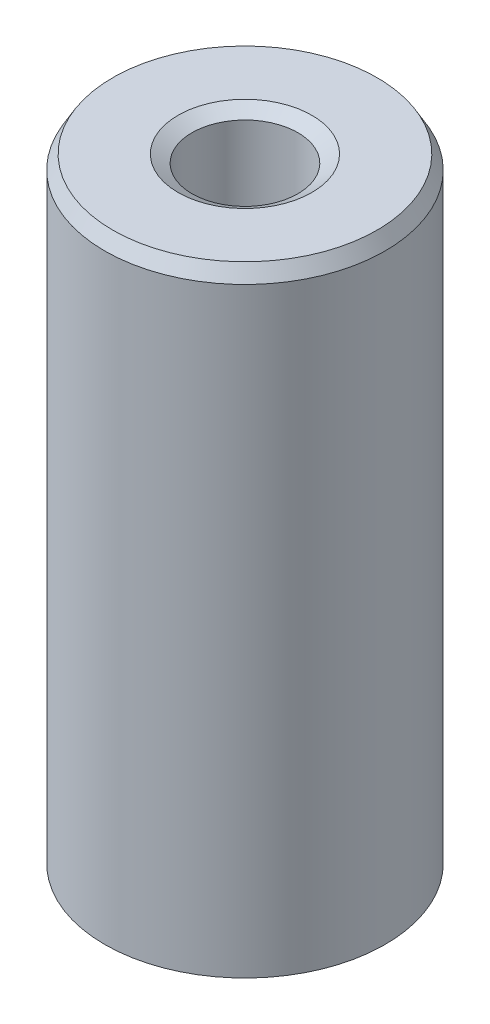
SolidWorks part; units mm, degrees
ref_plane "Front Plane" through (0, 0, 0) normal (0, 0, 1) x (1, 0, 0)
ref_plane "Top Plane" through (0, 0, 0) normal (0, 1, 0) x (1, 0, 0)
ref_plane "Right Plane" through (0, 0, 0) normal (1, 0, 0) x (0, 0, -1)
sketch "Sketch1" plane through (0, 0, 0) normal (0, 1, 0) x (1, 0, 0)
  circle A0 centre (0, 0) radius 12.5
  dimension "SLEEVE_OD" = 25
extrude "Boss-Extrude1" add sketch "Sketch1" along normal blind 55.5131
sketch "Sketch2" plane through (0, 0, 0) normal (0, 1, 0) x (1, 0, 0)
  circle A0 centre (0, 0) radius 4.7201
  dimension "BORE_D" = 9.4402
extrude "Cut-Extrude1" cut sketch "Sketch2" along normal through all
chamfer "Chamfer1" distance 1.2459 angle 30 4 edges at (0, 55.5131, 4.7201) (0, 0, 4.7201) (0, 0, 12.5) (0, 55.5131, 12.5) first distance on face at (0, 55.5131, 4.7201) first distance on face at (0, 0, 4.7201) first distance on face at (0, 55.5131, 12.5)
